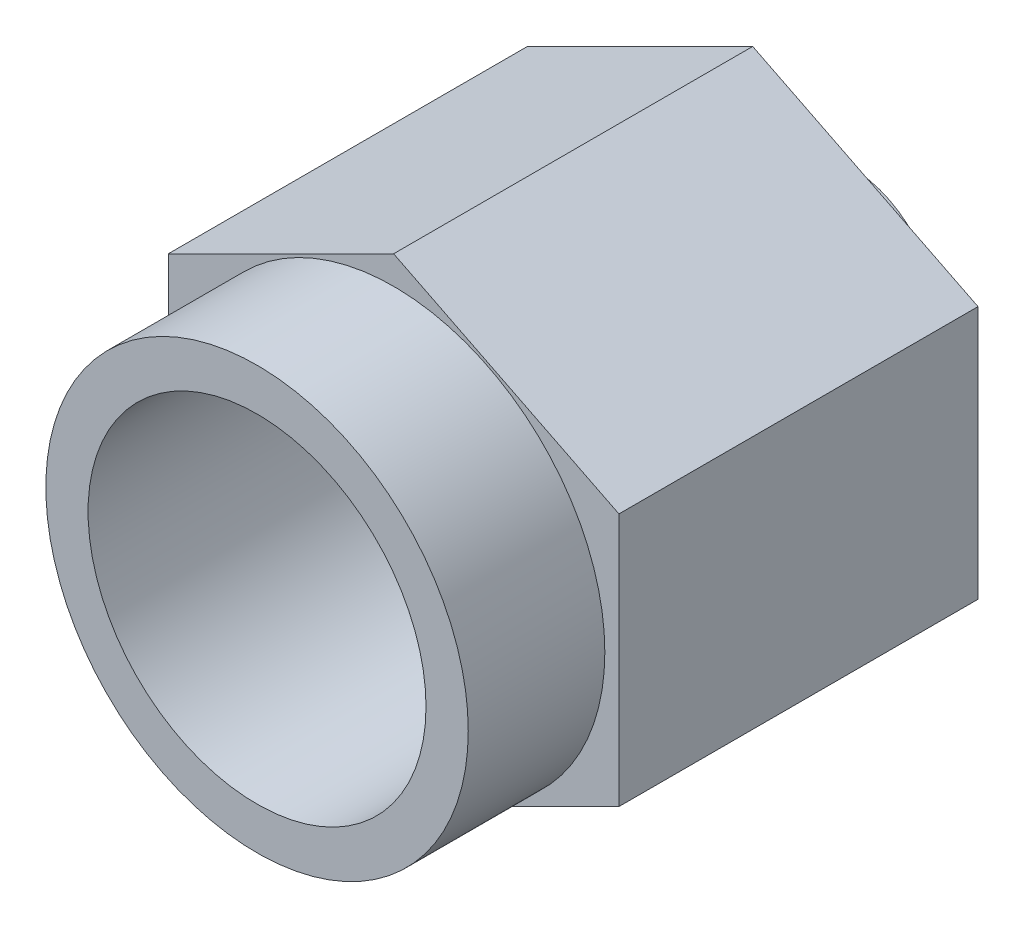
SolidWorks part; units mm, degrees
ref_plane "Plane1" through (0, 0, 0) normal (0, 0, 1) x (1, 0, 0)
ref_plane "Plane2" through (0, 0, 0) normal (0, 1, 0) x (1, 0, 0)
ref_plane "Plane3" through (0, 0, 0) normal (1, 0, 0) x (0, 0, -1)
sketch "Sketch1" plane through (0, 0, 0) normal (0, 0, 1) x (1, 0, 0)
  circle A0 centre (0, 0) radius 1.5367
  circle A1 centre (0, 0) radius 1.0795
  dimension "D1" = 3.0734
  dimension "D2" = 2.159
sketch "Sketch2" plane through (0, 0, 0) normal (0, 0, 1) x (1, 0, 0)
  circle A0 centre (0, 0) radius 3.048
  circle A1 centre (0, 0) radius 3.81
extrude "Base-Extrude" add sketch "Sketch2" along normal blind 8.9408
sketch "Sketch3" plane through (0, 0, 0) normal (0, 0, 1) x (1, 0, 0)
  line L0 (-4.064, 2.286) -> (-4.064, -2.286)
  line L1 (4.064, 2.286) -> (4.064, -2.286)
  line L2 (0, -4.318) -> (4.064, -2.286)
  line L3 (-4.064, -2.286) -> (0, -4.318)
  line L4 (0, 4.318) -> (-4.064, 2.286)
  line L5 (0, 4.318) -> (4.064, 2.286)
extrude "Boss-Extrude3" add sketch "Sketch3" along normal blind 6.477
sketch "Sketch4" plane through (0, 0, 0) normal (0, 0, 1) x (1, 0, 0)
  circle A0 centre (0, 0) radius 3.048
extrude "Cut-Extrude2" cut sketch "Sketch4" along normal blind 10
sketch "Sketch5" plane through (0, 0, 0) normal (0, 0, 1) x (1, 0, 0)
  circle A0 centre (0, 0) radius 3.048
  circle A1 centre (0, 0) radius 1.5367
  dimension "D1" = 3.0734
extrude "Boss-Extrude9" add sketch "Sketch5" against normal blind 0.508 and the other way blind 0.254
extrude "Boss-Extrude12" add sketch "Sketch1" along normal blind 1.778 and the other way blind 1.778
sketch "Sketch6" plane through (0, 0, -0.508) normal (0, 0, -1) x (-1, 0, 0)
  point P0 (0, 0)
other "CPoint1" parameters "Diameter"=4.7625, "StubLength"=7
ref_axis "Axis1" through (0, 0, -10.508) along (0, 0, 1)
